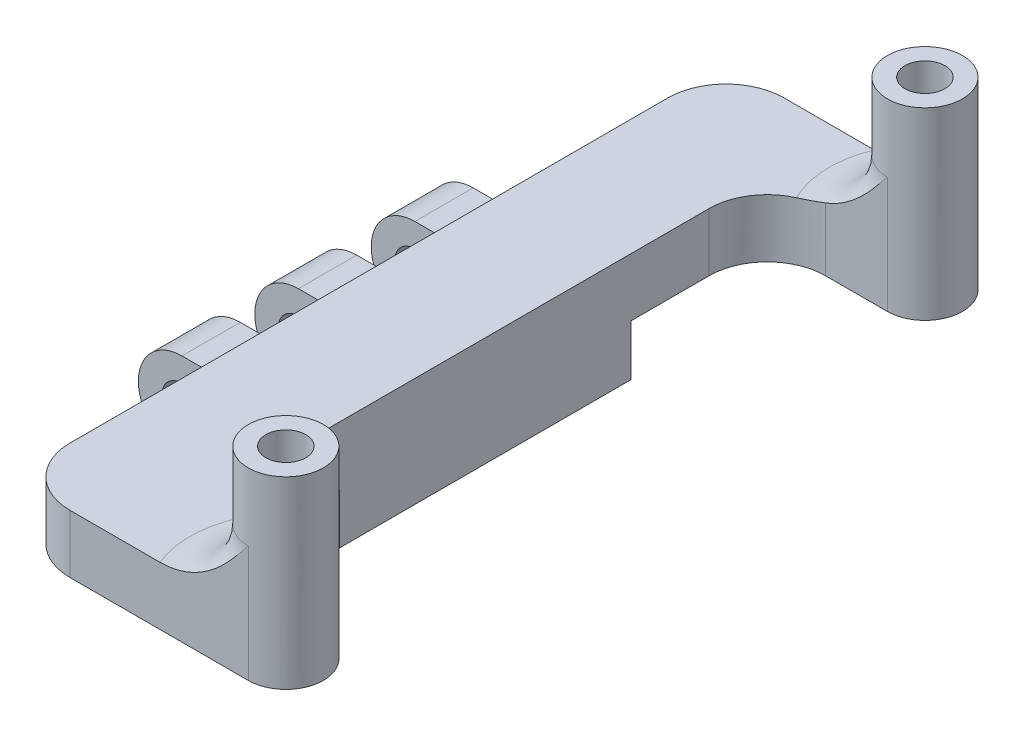
SolidWorks part; units mm, degrees
material "CARBON FIBER TEST"
ref_plane "Front Plane" through (0, 0, 0) normal (0, 0, 1) x (1, 0, 0)
ref_plane "Top Plane" through (0, 0, 0) normal (0, 1, 0) x (1, 0, 0)
ref_plane "Right Plane" through (0, 0, 0) normal (1, 0, 0) x (0, 0, -1)
sketch "Sketch2" plane through (0, 0, 0) normal (0, 0, 1) x (1, 0, 0)
  line L0 (0, 1.75) -> (8, 1.75)
  line L1 (8, 1.75) -> (8, -1.75)
  line L2 (8, -1.75) -> (0, -1.75)
  line L3 (0, -1.75) -> (0, 1.75)
  point P4 (0, 0)
  dimension "D2" = 3.5
  dimension "D3" = 8
extrude "Boss-Extrude1" add sketch "Sketch2" along normal mid plane 20
sketch "Sketch4" plane through (0, 0, 10) normal (0, 0, 1) x (1, 0, 0)
  line L0 (0, 4.25) -> (-2.8368, 4.25)
  line L1 (0, -1.75) -> (-2.8368, -1.75)
  line L2 (0, 4.25) -> (0, -1.75)
  arc A0 (-2.8368, 4.25) -> (-2.8368, -1.75) centre (-2.8368, 1.25) ccw
  circle A1 centre (-2.8368, 1.25) radius 1.375
  dimension "D1" = 6
  dimension "D3" = 2.75
  dimension "D2" = 3.1
extrude "Boss-Extrude2" add sketch "Sketch4" against normal blind 4
sketch "Sketch6" plane through (0, 1.75, 0) normal (0, 1, 0) x (1, 0, 0)
  line L3 (0, 24.535) -> (0, -24.535)
  line L4 (0, -24.535) -> (16.25, -24.535)
  line L6 (16.25, -19.375) -> (8, -19.375)
  line L7 (8, -19.375) -> (8, 19.375)
  line L8 (8, 19.375) -> (16.25, 19.375)
  line L10 (16.25, 24.535) -> (0, 24.535)
  line L12 (8.5, 16) -> (18.5, 16) construction
  line L13 (8.5, 16) -> (8.5, -16) construction
  line L14 (8.5, -16) -> (18.5, -16) construction
  line L15 (18.5, 16) -> (18.5, -16) construction
  line L16 (8.5, 16) -> (18.5, -16) construction
  line L17 (8.5, -16) -> (18.5, 16) construction
  arc A0 (16.25, 19.375) -> (16.25, 24.535) centre (16.25, 21.955) ccw
  arc A1 (16.25, -24.535) -> (16.25, -19.375) centre (16.25, -21.955) ccw
  point P2 (13.5, 0)
  point P16 (36.5034, 16)
  point P17 (0, 0)
  dimension "D5" = 2.58
  dimension "D1" = 8
  dimension "D2" = 0.5
  dimension "D3" = 43.91
  dimension "D4" = 32
  dimension "D6" = 8.25
  dimension "D7" = 10
extrude "Boss-Extrude3" add sketch "Sketch6" along normal blind 4
sketch "Sketch7" plane through (0, 5.75, 0) normal (0, 1, 0) x (1, 0, 0)
  circle A0 centre (16.25, 21.955) radius 2.58
  circle A1 centre (16.25, -21.955) radius 2.58
  arc A6 (16.25, 19.375) -> (16.25, 24.535) centre (16.25, 21.955) ccw construction
  arc A7 (16.25, -24.535) -> (16.25, -19.375) centre (16.25, -21.955) ccw construction
  dimension "D1" = 2.58
extrude "Boss-Extrude4" add sketch "Sketch7" along normal offset from surface (8.65 mm away) 16.15 up to face at (1.7211, -1.75, 2)
sketch "Sketch8" plane through (0, 14.4, 0) normal (0, 1, 0) x (1, 0, 0)
  circle A0 centre (16.25, 21.955) radius 1.375
  circle A1 centre (16.25, -21.955) radius 1.375
  circle A2 centre (16.25, -21.955) radius 2.58 construction
  circle A4 centre (16.25, 21.955) radius 2.58 construction
  dimension "D1" = 2.75
extrude "Cut-Extrude1" cut sketch "Sketch8" against normal through all
fillet "Fillet1" radius 4 4 edges at (13.67, 5.75, 21.955) (13.67, 5.75, -21.955) (0, 3.75, -24.535) (0, 3.75, 24.535)
fillet "Fillet2" radius 4 2 edges at (8, 3.75, -19.375) (8, 3.75, 19.375)
pattern_linear "LPattern1" count 3 spacing 8 along (0, 0, -1) of "Boss-Extrude2"
equation "\"D19@Boss-Extrude2\"=(15.43mm/5)"
equation "\"JointWidth\"= 4mm"
equation "\"D1@Boss-Extrude1\"=\"JointWidth\"*5"
equation "\"D3@LPattern1\"=\"JointWidth\"*2"
equation "\"D1@Boss-Extrude2\"=\"JointWidth\""
